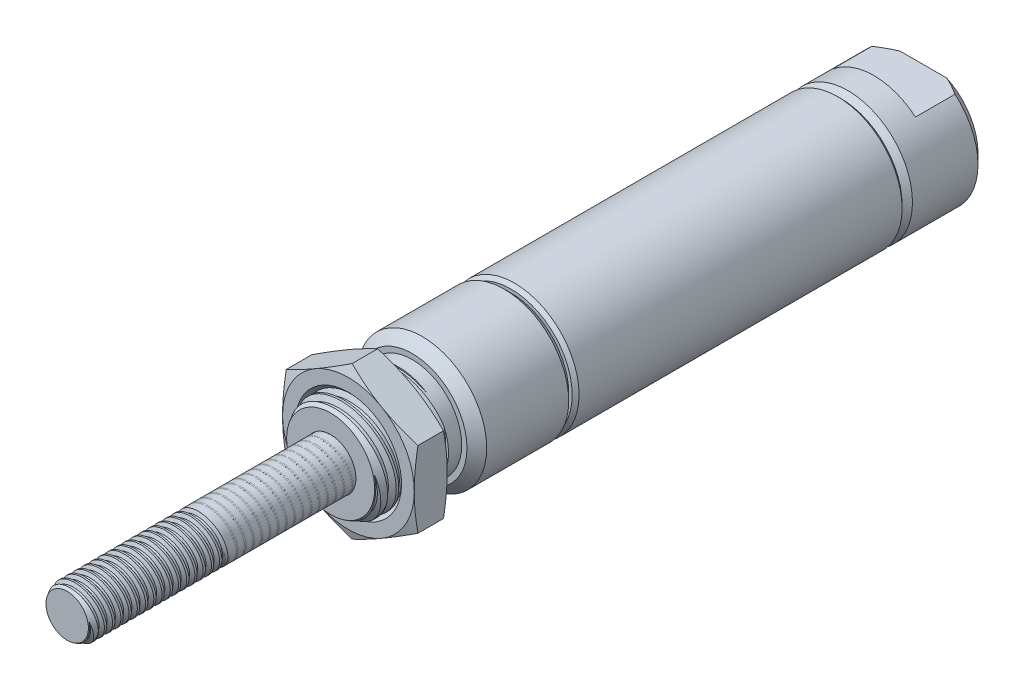
SolidWorks part; units mm, degrees
ref_plane "Front" through (0, 0, 0) normal (0, 0, 1) x (1, 0, 0)
ref_plane "Top" through (0, 0, 0) normal (0, 1, 0) x (1, 0, 0)
ref_plane "Right" through (0, 0, 0) normal (1, 0, 0) x (0, 0, -1)
sketch "Sketch1" plane through (0, 0, 0) normal (1, 0, 0) x (0, 0, -1)
  line L0 (-34.925, 0) -> (34.925, 0) construction
  line L1 (-22.225, -4.7625) -> (-22.225, 0) construction
  line L2 (-22.225, 4.7625) -> (-14.351, 4.7625) construction
  line L3 (-14.351, 0) -> (-14.351, 6.223)
  line L4 (-14.351, 6.223) -> (34.925, 6.223)
  line L5 (30.1625, 6.223) -> (30.1625, 4.7625) construction
  line L6 (30.1625, 4.7625) -> (34.925, 4.7625) construction
  line L7 (34.925, 6.223) -> (34.925, 0)
  line L8 (34.925, 0) -> (39.6875, 0) construction
  line L9 (-22.225, -4.7625) -> (-14.351, -4.7625) construction
  line L10 (-14.351, -4.7625) -> (-14.351, -6.223) construction
  line L11 (-14.351, -6.223) -> (34.925, -6.223) construction
  line L12 (30.1625, -6.223) -> (30.1625, -4.7625) construction
  line L13 (30.1625, -4.7625) -> (34.925, -4.7625) construction
  line L14 (-15.621, 4.7625) -> (-15.621, 0) construction
  line L18 (-22.225, 2.413) -> (-34.925, 2.413) construction
  line L19 (-34.925, 2.413) -> (-34.925, -2.413) construction
  line L20 (-34.925, -2.413) -> (-22.225, -2.413) construction
  line L24 (-22.225, 2.413) -> (-15.621, 2.413) construction
  line L25 (34.925, 0) -> (34.925, -6.223) construction
  line L26 (-22.225, 0) -> (-22.225, 4.7625) construction
  line L28 (-14.351, 0) -> (34.925, 0)
  line L29 (-18.923, 2.413) -> (-18.923, 4.7625) construction
  dimension "J Flat" = 9.525
  dimension "E OD" = 12.446
  dimension "K Flat Depth" = 4.7625
  dimension "RM Pilot" = 9.525
  dimension "G Pilot Length" = 7.874
  dimension "Shaft Dia" = 4.826
  dimension "A Thread Length" = 12.7
  dimension "Total Length" = 69.85
  dimension "V Pilot Length" = 1.27
revolve "Revolve1" add sketch "Sketch1" angle 360 about L8 reverse direction yes
sketch "Sketch2" plane through (0, 0, 0) normal (1, 0, 0) x (0, 0, -1)
  line L0 (-14.351, 6.223) -> (34.925, 6.223) construction
  line L1 (34.925, 6.223) -> (34.925, 0) construction
  line L2 (34.925, 0) -> (34.925, -6.223) construction
  line L3 (-14.351, -6.223) -> (34.925, -6.223) construction
  line L4 (30.1625, -6.223) -> (30.1625, -4.7625) construction
  line L5 (30.1625, -4.7625) -> (34.925, -4.7625) construction
  line L6 (30.1625, 4.7625) -> (34.925, 4.7625) construction
  line L7 (30.1625, 6.223) -> (30.1625, 4.7625) construction
  line L8 (30.1625, 6.223) -> (34.925, 6.223)
  line L9 (34.925, 6.223) -> (34.925, 4.7625)
  line L10 (34.925, -4.7625) -> (34.925, -6.223)
  line L11 (30.1625, -6.223) -> (34.925, -6.223)
  line L12 (30.1625, -6.223) -> (30.1625, -4.7625)
  line L13 (30.1625, -4.7625) -> (34.925, -4.7625)
  line L14 (30.1625, 4.7625) -> (34.925, 4.7625)
  line L15 (30.1625, 6.223) -> (30.1625, 4.7625)
extrude "Cut-Extrude1" cut sketch "Sketch2" against normal through all and the other way through all
chamfer "Chamfer1" distance 0.9525 angle 45 3 edges at (-6.223, 0, -34.925) (6.223, 0, -34.925) (-6.223, 0, 14.351)
sketch "Sketch4" plane through (0, 0, 0) normal (1, 0, 0) x (0, 0, -1)
  line L0 (-22.225, 0) -> (-22.225, 4.7625) construction
  line L1 (-34.925, 0) -> (34.925, 0) construction
  line L2 (-14.351, 0) -> (-14.351, 6.223) construction
  line L3 (-22.225, 4.7625) -> (-14.351, 4.7625) construction
  line L4 (-22.225, 0) -> (-22.225, 4.7625)
  line L5 (-22.225, 0) -> (-14.351, 0)
  line L6 (-14.351, 0) -> (-14.351, 4.7625)
  line L7 (-22.225, 4.7625) -> (-14.351, 4.7625)
  line L8 (-22.225, -4.7625) -> (-14.351, -4.7625) construction
  line L9 (-22.225, -4.7625) -> (-14.351, -4.7625) construction
revolve "Revolve2" add sketch "Sketch4" angle 360 about L5
sketch "Sketch5" plane through (0, 0, 0) normal (1, 0, 0) x (0, 0, -1)
  line L0 (-22.225, 4.7625) -> (-22.225, -4.7625) construction
  line L1 (-22.225, -4.7625) -> (-21.1667, -4.7625) construction
  line L2 (-21.1667, -4.7625) -> (-22.225, 4.7625) construction
  line L3 (-22.225, 4.7625) -> (-22.0935, 4.7771) construction
  line L4 (-22.0935, 4.7771) -> (-21.1731, 4.8794)
  line L5 (-21.1731, 4.8794) -> (-21.4386, 4.2735)
  line L6 (-21.4386, 4.2735) -> (-21.7016, 4.2443)
  line L7 (-21.7016, 4.2443) -> (-22.0935, 4.7771)
  line L8 (-21.6333, 4.8282) -> (-21.5701, 4.2589) construction
  line L9 (-22.225, 4.7625) -> (-21.626, 4.7625) construction
  line L10 (-21.626, 4.7625) -> (-20.5677, -4.7625) construction
  line L11 (-20.5677, -4.7625) -> (-21.1667, -4.7625) construction
  line L12 (-22.225, 0) -> (-22.225, 4.7625) construction
  line L13 (-22.225, 4.7625) -> (-14.351, 4.7625) construction
  line L14 (-22.225, -4.7625) -> (-14.351, -4.7625) construction
  line L15 (-22.225, -0.1253) -> (-19.9687, 0.1253) construction
  point P19 (-21.0969, 0)
  dimension "D1" = 0.1323
  dimension "D2" = 0.2646
  dimension "Thread Pitch" = 1.0583
  dimension "D4" = 60
  dimension "D5" = 1.0583
revolve "Cut-Revolve2" cut sketch "Sketch5" angle 360 about L15
sketch "Sketch6" plane through (0, 0, 0) normal (1, 0, 0) x (0, 0, -1)
  line L0 (-22.225, 4.2443) -> (-21.3274, 4.7625)
  line L1 (-21.3274, 4.7625) -> (-22.225, 4.7625)
  line L2 (-22.225, 4.7625) -> (-22.225, 4.2443)
  line L3 (0, 0) -> (-22.225, 0) construction
  line L4 (-22.225, 0) -> (-22.225, 4.2443) construction
  line L5 (-22.225, 4.7625) -> (-14.351, 4.7625) construction
  line L6 (-22.225, 0) -> (-22.225, 4.7625) construction
  line L7 (-21.7016, 4.2443) -> (-22.225, 4.2443) construction
  dimension "D1" = 60
revolve "Cut-Revolve3" cut sketch "Sketch6" angle 360 about L3
pattern_linear "LPattern2" count 2 spacing 1.0583 along (0, 0, 1) count 7 spacing 1.0583 along (0, 0, -1) of "Cut-Revolve2"
sketch "Sketch53" plane through (0, 0, 0) normal (1, 0, 0) x (0, 0, -1)
  line L0 (-22.225, 0) -> (-14.351, 0) construction
  line L1 (-14.351, 4.7625) -> (-15.621, 4.7625)
  line L2 (-14.351, 4.7625) -> (-14.351, 0)
  line L3 (-14.351, 0) -> (-15.621, 0)
  line L4 (-15.621, 4.7625) -> (-15.621, 0)
  line L5 (-15.621, 4.7625) -> (-15.621, 0) construction
revolve "Revolve4" add sketch "Sketch53" angle 360 about L3
sketch "Sketch7" plane through (0, 0, 0) normal (1, 0, 0) x (0, 0, -1)
  line L0 (-22.225, 2.4384) -> (-11.176, 2.4384)
  line L1 (-11.176, 2.4384) -> (-11.176, 3.9973)
  line L2 (-11.176, 5.5562) -> (-1.651, 5.5562) construction
  line L3 (11.049, 5.5562) -> (23.749, 5.5562)
  line L4 (23.749, 0) -> (-22.225, 0)
  line L5 (-22.225, 0) -> (-22.225, 2.4384)
  line L6 (-22.225, 0) -> (-22.225, 4.7625) construction
  line L7 (-14.351, 0) -> (34.925, 0) construction
  line L8 (23.749, 0) -> (39.6875, 0) construction
  line L9 (-14.351, 0) -> (-14.351, 6.223) construction
  line L10 (23.749, 5.5562) -> (23.749, 0)
  line L11 (-22.225, 2.413) -> (-34.925, 2.413) construction
  line L12 (-11.176, 3.9973) -> (-1.651, 3.9973)
  line L13 (-1.651, 3.9973) -> (-1.651, 5.5562)
  line L14 (-11.176, 3.9973) -> (-11.176, 5.5562) construction
  line L15 (-1.651, 5.5562) -> (11.049, 5.5562)
  dimension "D1" = 0.0254
  dimension "D2" = 12.7
  dimension "D3" = 9.525
  dimension "Stroke" = 12.7
  dimension "D4" = 3.175
  dimension "D6" = 11.1125
revolve "Cut-Revolve5" cut sketch "Sketch7" angle 360 about L8
sketch "Sketch3" plane through (0, 0, 0) normal (1, 0, 0) x (0, 0, -1)
  line L0 (27.6542, 6.223) -> (26.9875, 5.5562)
  line L1 (26.9875, 5.5562) -> (26.9875, 5.8896)
  line L2 (26.6541, 6.223) -> (27.6542, 6.223)
  line L3 (-4.826, 6.223) -> (-4.826, 5.8896) construction
  line L4 (-4.826, 5.5562) -> (-5.4928, 6.223)
  line L5 (-5.4928, 6.223) -> (-4.4926, 6.223)
  line L6 (-14.351, 6.223) -> (34.925, 6.223) construction
  line L7 (-4.826, 5.5562) -> (26.9875, 5.5562) construction
  line L8 (26.9875, 5.8896) -> (-4.826, 5.8896) construction
  line L9 (-14.351, 0) -> (-14.351, 6.223) construction
  line L10 (30.1625, 6.223) -> (30.1625, 4.7625) construction
  line L11 (34.925, 0) -> (39.6875, 0) construction
  line L12 (34.925, 0) -> (39.6875, 0) construction
  line L13 (26.9875, 5.8896) -> (26.6541, 6.223)
  line L14 (26.9875, 5.8896) -> (26.9875, 6.223) construction
  line L15 (-4.826, 5.8896) -> (-4.4926, 6.223)
  line L16 (-4.826, 5.8896) -> (-4.826, 5.5562)
  line L18 (-1.651, 5.5562) -> (11.049, 5.5562) construction
  dimension "D1" = 9.525
  dimension "D2" = 3.175
  dimension "D4" = 45
revolve "Cut-Revolve1" cut sketch "Sketch3" angle 360 about L12
sketch "Sketch8" plane through (0, 0, 0) normal (1, 0, 0) x (0, 0, -1)
  line L0 (-22.225, 2.413) -> (-34.925, 2.413) construction
  line L1 (11.049, 2.413) -> (11.049, 5.5054)
  line L2 (11.049, 5.5054) -> (23.749, 5.5054)
  line L3 (23.749, 5.5054) -> (23.749, 0)
  line L4 (-34.925, 2.413) -> (-34.925, -2.413) construction
  line L5 (11.049, 2.413) -> (-34.925, 2.413)
  line L6 (-34.925, 2.413) -> (-34.925, 0)
  line L7 (23.749, 0) -> (-34.925, 0)
  line L8 (-34.925, 0) -> (34.925, 0) construction
  line L9 (11.049, 5.5562) -> (23.749, 5.5562) construction
  line L11 (23.749, 5.5562) -> (23.749, 0) construction
  dimension "D1" = 0.0508
  dimension "D2" = 12.7
revolve "Revolve3" add sketch "Sketch8" angle 360 about L7
sketch "Sketch10" plane through (0, 0, 0) normal (1, 0, 0) x (0, 0, -1)
  line L0 (-34.925, 2.413) -> (-34.925, -2.413) construction
  line L1 (-34.925, -2.413) -> (-34.1312, -2.413) construction
  line L2 (-34.1312, -2.413) -> (-34.925, 2.413) construction
  line L3 (-34.925, 2.413) -> (-34.8271, 2.4291) construction
  line L4 (-34.8271, 2.4291) -> (-34.1418, 2.5418)
  line L5 (-34.1418, 2.5418) -> (-34.3168, 2.0776)
  line L6 (-34.3168, 2.0776) -> (-34.5126, 2.0454)
  line L7 (-34.5126, 2.0454) -> (-34.8271, 2.4291)
  line L8 (-34.4844, 2.4855) -> (-34.4147, 2.0615) construction
  line L9 (-34.925, 2.413) -> (-34.4725, 2.413) construction
  line L10 (-34.4725, 2.413) -> (-33.6788, -2.413) construction
  line L11 (-33.6788, -2.413) -> (-34.1312, -2.413) construction
  line L12 (-34.925, 2.413) -> (-34.925, -2.413) construction
  line L13 (-22.225, 2.413) -> (-34.925, 2.413) construction
  line L14 (-34.925, -2.413) -> (-22.225, -2.413) construction
  line L15 (-34.925, -0.1397) -> (-33.2263, 0.1397) construction
  point P19 (-34.0756, 0)
  dimension "D1" = 0.0992
  dimension "D2" = 0.1984
  dimension "Shaft Thread Pitch" = 0.7937
  dimension "D4" = 0.7937
  dimension "D5" = 60
revolve "Cut-Revolve6" cut sketch "Sketch10" angle 360 about L15
sketch "Sketch11" plane through (0, 0, 0) normal (1, 0, 0) x (0, 0, -1)
  line L0 (-34.925, 2.413) -> (-34.2883, 2.413)
  line L1 (-34.2883, 2.413) -> (-34.925, 2.0454)
  line L2 (-34.925, 2.0454) -> (-34.925, 2.413)
  line L3 (0, 0) -> (-34.925, 0) construction
  line L4 (-34.925, 0) -> (-34.925, 2.0454) construction
  line L5 (-22.225, 2.413) -> (-34.925, 2.413) construction
  line L6 (-34.925, 2.413) -> (-34.925, -2.413) construction
  line L7 (-34.5126, 2.0454) -> (-34.925, 2.0454) construction
  dimension "D1" = 30
revolve "Cut-Revolve7" cut sketch "Sketch11" angle 360 about L3
pattern_linear "LPattern3" count 2 spacing 0.7937 along (0, 0, 1) count 16 spacing 0.7937 along (0, 0, -1) of "Cut-Revolve6"
pattern_linear "LPattern4" count 2 spacing 12.7 along (0, 0, 1) of bodies 122
ref_axis "Axis1" through (0, -6.8453, 0) along (0, 1, 0)
ref_plane "Plane1" through (0, 0, 0) normal (-1, 0, 0) x (0, 0, 1)
sketch "Sketch13" plane through (0, -1.7517, 219.4497) normal (1, 0, 0) x (0, 0, -1)
  line L0 (247.3897, 1.7517) -> (247.3897, 3.821)
  line L1 (247.3897, 3.821) -> (247.7866, 4.5084) construction
  line L2 (247.7866, 4.5084) -> (248.1834, 3.821) construction
  line L3 (248.1834, 3.821) -> (248.5803, 4.5084) construction
  line L4 (248.5803, 4.5084) -> (248.9772, 3.821) construction
  line L5 (248.1986, 3.8472) -> (248.5652, 4.4822)
  line L6 (248.5652, 4.4822) -> (248.5954, 4.4822)
  line L7 (248.5954, 4.4822) -> (248.9621, 3.8472)
  line L8 (248.9621, 3.8472) -> (248.9923, 3.8472)
  line L9 (247.3897, 3.821) -> (248.9772, 3.821) construction
  line L10 (247.7866, 4.5084) -> (248.5803, 4.5084) construction
  line L11 (247.5881, 4.1647) -> (248.7788, 4.1647) construction
  line L12 (247.3897, 1.7517) -> (245.3204, 1.7517) construction
  line L13 (248.9923, 3.8472) -> (249.359, 4.4822)
  line L14 (247.4048, 3.8472) -> (247.7715, 4.4822)
  line L15 (247.7715, 4.4822) -> (247.8017, 4.4822)
  line L16 (247.8017, 4.4822) -> (248.1683, 3.8472)
  line L17 (248.1683, 3.8472) -> (248.1986, 3.8472)
  line L18 (247.5881, 4.1647) -> (247.3897, 4.1647) construction
  line L19 (247.3897, 4.1647) -> (247.3897, 3.821) construction
  line L20 (247.5881, -0.6613) -> (247.3897, -0.6613) construction
  line L21 (247.4048, 3.8472) -> (247.3897, 3.821)
  line L22 (249.359, 4.4822) -> (249.3892, 4.4822)
  line L23 (249.3892, 4.4822) -> (249.7558, 3.8472)
  line L24 (249.7558, 3.8472) -> (249.7861, 3.8472)
  line L25 (249.7861, 3.8472) -> (250.1527, 4.4822)
  line L26 (250.1527, 4.4822) -> (250.1829, 4.4822)
  line L27 (250.1829, 4.4822) -> (250.5496, 3.8472)
  line L28 (250.5496, 3.8472) -> (250.5798, 3.8472)
  line L29 (250.5798, 3.8472) -> (250.9465, 4.4822)
  line L30 (250.9465, 4.4822) -> (250.9767, 4.4822)
  line L31 (250.9767, 4.4822) -> (251.3433, 3.8472)
  line L32 (251.3433, 3.8472) -> (251.3736, 3.8472)
  line L33 (251.3736, 3.8472) -> (251.7402, 4.4822)
  line L34 (251.7402, 4.4822) -> (251.7704, 4.4822)
  line L35 (251.7704, 4.4822) -> (252.1371, 3.8472)
  line L36 (252.1371, 3.8472) -> (252.1673, 3.8472)
  line L37 (252.1673, 3.8472) -> (252.534, 4.4822)
  line L38 (252.534, 4.4822) -> (252.5642, 4.4822)
  line L39 (252.5642, 4.4822) -> (252.9308, 3.8472)
  line L40 (252.9308, 3.8472) -> (252.9611, 3.8472)
  line L41 (252.9611, 3.8472) -> (253.3277, 4.4822)
  line L42 (253.3277, 4.4822) -> (253.3579, 4.4822)
  line L43 (253.3579, 4.4822) -> (253.7246, 3.8472)
  line L44 (253.7246, 3.8472) -> (253.7548, 3.8472)
  line L45 (253.7548, 3.8472) -> (254.1215, 4.4822)
  line L46 (254.1215, 4.4822) -> (254.1517, 4.4822)
  line L47 (254.1517, 4.4822) -> (254.5183, 3.8472)
  line L48 (254.5183, 3.8472) -> (254.5486, 3.8472)
  line L49 (254.5486, 3.8472) -> (254.9152, 4.4822)
  line L50 (254.9152, 4.4822) -> (254.9454, 4.4822)
  line L51 (254.9454, 4.4822) -> (255.3121, 3.8472)
  line L52 (255.3121, 3.8472) -> (255.3423, 3.8472)
  line L53 (255.3423, 3.8472) -> (255.709, 4.4822)
  line L54 (255.709, 4.4822) -> (255.7392, 4.4822)
  line L55 (255.7392, 4.4822) -> (256.1058, 3.8472)
  line L56 (256.1058, 3.8472) -> (256.1361, 3.8472)
  line L57 (256.1361, 3.8472) -> (256.5027, 4.4822)
  line L58 (256.5027, 4.4822) -> (256.5329, 4.4822)
  line L59 (256.5329, 4.4822) -> (256.8996, 3.8472)
  line L60 (256.8996, 3.8472) -> (256.9298, 3.8472)
  line L61 (256.9298, 3.8472) -> (257.2965, 4.4822)
  line L62 (257.2965, 4.4822) -> (257.3267, 4.4822)
  line L63 (257.3267, 4.4822) -> (257.6933, 3.8472)
  line L64 (257.6933, 3.8472) -> (257.7236, 3.8472)
  line L65 (257.7236, 3.8472) -> (258.0902, 4.4822)
  line L66 (258.0902, 4.4822) -> (258.1204, 4.4822)
  line L67 (258.1204, 4.4822) -> (258.4871, 3.8472)
  line L68 (258.4871, 3.8472) -> (258.5173, 3.8472)
  line L69 (258.5173, 3.8472) -> (258.884, 4.4822)
  line L70 (258.884, 4.4822) -> (258.9142, 4.4822)
  line L71 (258.9142, 4.4822) -> (259.2808, 3.8472)
  line L72 (259.2808, 3.8472) -> (259.3111, 3.8472)
  line L73 (247.3897, 1.7517) -> (259.3111, 1.7517)
  line L74 (259.3111, 1.7517) -> (259.3111, 3.8472)
  line L75 (247.7866, 4.4822) -> (247.7866, 4.5084) construction
  line L76 (248.7788, 4.1647) -> (252.4697, 4.1647) construction
  line L77 (252.4697, 4.1647) -> (252.4697, 1.7517) construction
  line L78 (252.4697, 4.1647) -> (254.3747, 4.1647) construction
  line L79 (254.3747, 4.1647) -> (254.3747, 1.7517) construction
  line L82 (254.3747, 7.9747) -> (254.3747, 1.7517) construction
  line L84 (252.4697, 3.8472) -> (254.3747, 3.8472) construction
  dimension "D1" = 60
  dimension "D2" = 0.0262
  dimension "E0" = 4.826
  dimension "D3" = 0.0302
  dimension "Thread Pitch" = 0.7937
  dimension "L2 Thread Engagement" = 5.08
  dimension "L4 Thread Length" = 6.985
revolve "Cut-Revolve22" cut sketch "Sketch13" angle 360 about L12
sketch "Sketch52" plane through (0, 0, 0) normal (1, 0, 0) x (0, 0, -1)
  line L0 (27.94, 0) -> (27.94, 2.0693) construction
  line L1 (27.94, 1.0346) -> (23.749, 1.0346)
  line L2 (27.94, 1.0346) -> (27.94, 0)
  line L3 (27.94, 0) -> (23.749, 0)
  line L4 (23.749, 1.0346) -> (23.749, 0)
revolve "Cut-Revolve23" cut sketch "Sketch52" angle 360 about L3
ref_plane "Plane2" through (0, 0, 18.923) normal (0, 0, 1) x (1, 0, 0)
sketch "Sketch54" plane through (0, 0, 18.923) normal (0, 0, 1) x (1, 0, 0)
  line L1 (0, 7.3323) -> (-6.35, 3.6662)
  line L2 (-6.35, 3.6662) -> (-6.35, -3.6662)
  line L3 (-6.35, -3.6662) -> (0, -7.3323)
  line L4 (0, -7.3323) -> (6.35, -3.6662)
  line L5 (6.35, -3.6662) -> (6.35, 3.6662)
  line L6 (6.35, 3.6662) -> (0, 7.3323)
  circle A0 centre (0, 0) radius 6.35 construction
  circle A1 centre (0, 0) radius 4.7625
  dimension "Nut Hex" = 12.7
extrude "Extrude1" add sketch "Sketch54" along normal mid plane 3.175 separate body
sketch "Sketch55" plane through (0, 0, 0) normal (1, 0, 0) x (0, 0, -1)
  line L0 (-20.153, 7.3323) -> (-20.5105, 7.3323)
  line L1 (-20.5105, 7.3323) -> (-20.5105, 6.35)
  line L2 (-20.5105, 6.35) -> (-20.153, 7.3323)
  line L3 (-17.693, 7.3323) -> (-17.3355, 7.3323)
  line L4 (-17.3355, 7.3323) -> (-17.3355, 6.35)
  line L5 (-17.3355, 6.35) -> (-17.693, 7.3323)
  line L6 (-20.5105, 6.35) -> (-17.3355, 6.35) construction
  line L7 (-20.5105, 7.3323) -> (-17.3355, 7.3323) construction
  line L8 (-20.5105, 3.6662) -> (-20.5105, 7.3323) construction
  line L9 (-17.3355, 3.6662) -> (-17.3355, 7.3323) construction
  line L10 (0, 0) -> (-20.5105, 0) construction
  line L11 (-20.5105, 0) -> (-20.5105, 6.35) construction
  line L12 (-20.5105, 5.12) -> (-20.5105, 4.7625)
  line L13 (-20.5105, 4.7625) -> (-20.153, 4.7625)
  line L14 (-20.153, 4.7625) -> (-20.5105, 5.12)
  line L15 (-17.3355, 5.12) -> (-17.3355, 4.7625)
  line L16 (-17.3355, 4.7625) -> (-17.693, 4.7625)
  line L17 (-17.693, 4.7625) -> (-17.3355, 5.12)
  line L18 (-17.3355, 4.7625) -> (-20.5105, 4.7625) construction
  line L19 (-20.153, 7.3323) -> (-20.153, 4.7625) construction
  dimension "D1" = 20
  dimension "D2" = 12.7
  dimension "D3" = 45
revolve "Cut-Revolve24" cut sketch "Sketch55" angle 360 about L10
equation "\"D1@Chamfer1\"=\"K Flat Depth@Sketch1\"/5"
equation "\"D1@Sketch5\"=\"Thread Pitch@Sketch5\"/8"
equation "\"D2@Sketch5\"=\"Thread Pitch@Sketch5\"/4"
equation "\"D5@Sketch5\"=\"Thread Pitch@Sketch5\""
equation "\"D3@LPattern2\"=\"Thread Pitch@Sketch5\""
equation "\"D4@LPattern2\"=\"Thread Pitch@Sketch5\""
equation "\"D2@LPattern2\"=\"G Pilot Length@Sketch1\"/\"Thread Pitch@Sketch5\""
equation "\"D1@Sketch10\"=\"Shaft Thread Pitch@Sketch10\"/8"
equation "\"D2@Sketch10\"=\"Shaft Thread Pitch@Sketch10\"/4"
equation "\"D4@Sketch10\"=\"Shaft Thread Pitch@Sketch10\""
equation "\"D3@LPattern3\"=\"Shaft Thread Pitch@Sketch10\""
equation "\"D4@LPattern3\"=\"Shaft Thread Pitch@Sketch10\""
equation "\"D2@LPattern3\"=\"A Thread Length@Sketch1\"/\"Shaft Thread Pitch@Sketch10\""
equation "\"D3@LPattern4\"=\"Stroke@Sketch7\""
equation "\"D2@Sketch13\"=\"Thread Pitch@Sketch13\"*.033"
equation "\"D2@Sketch55\"=\"Nut Hex@Sketch54\""
